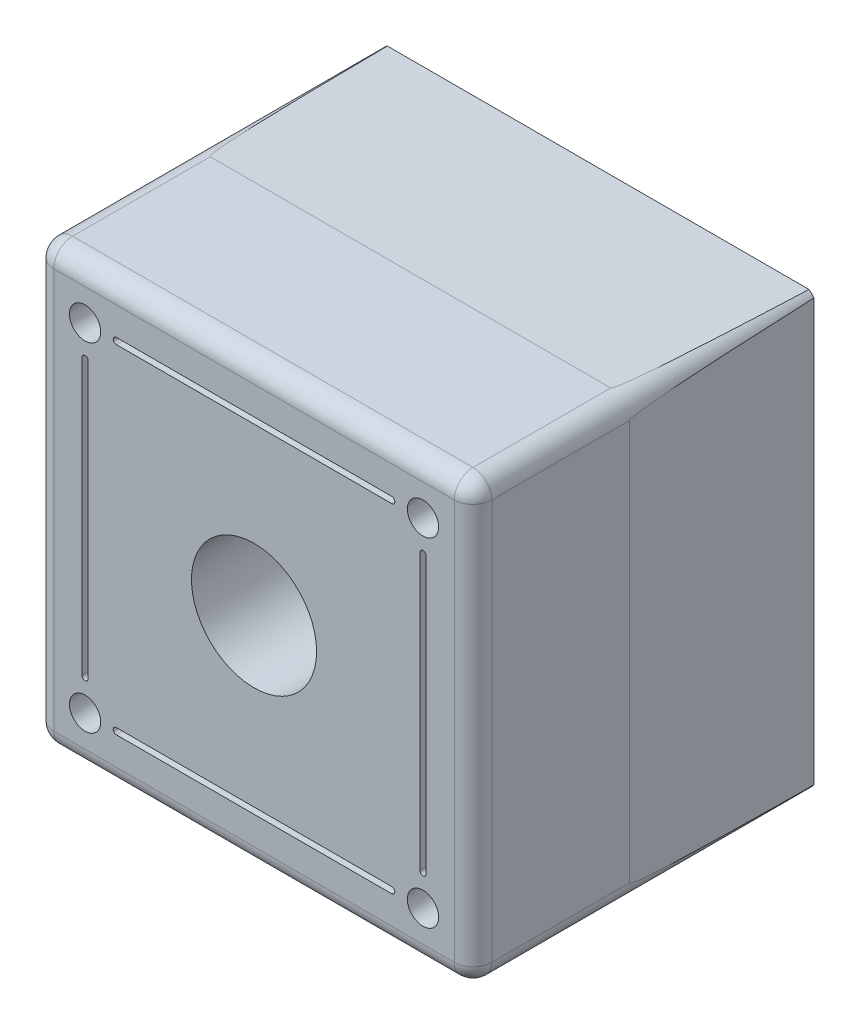
SolidWorks part; units mm, degrees
ref_plane "Front Plane" through (0, 0, 0) normal (0, 0, 1) x (1, 0, 0)
ref_plane "Top Plane" through (0, 0, 0) normal (0, 1, 0) x (1, 0, 0)
ref_plane "Right Plane" through (0, 0, 0) normal (1, 0, 0) x (0, 0, -1)
sketch "Sketch1" plane through (0, 0, 0) normal (0, 0, 1) x (1, 0, 0)
  line L1 (-35, 35) -> (35, 35)
  line L2 (-35, 35) -> (-35, -35)
  line L3 (-35, -35) -> (35, -35)
  line L4 (35, 35) -> (35, -35)
  line L5 (-35, 35) -> (35, -35) construction
  line L6 (-35, -35) -> (35, 35) construction
  point P0 (0, 0)
  dimension "D1" = 70
  dimension "D2" = 70
extrude "Boss-Extrude1" add sketch "Sketch1" against normal blind 30 draft 1
sketch "Sketch2" plane through (0, 0, 0) normal (0, 0, 1) x (1, 0, 0)
  line L4 (35, -35) -> (35, 35)
  line L5 (35, 35) -> (-35, 35)
  line L6 (-35, 35) -> (-35, -35)
  line L7 (-35, -35) -> (35, -35)
  line L8 (35, -35) -> (35, 35)
  line L9 (35, 35) -> (-35, 35)
  line L10 (-35, 35) -> (-35, -35)
  line L11 (-35, -35) -> (35, -35)
  dimension "D1" = 0
extrude "Boss-Extrude2" add sketch "Sketch2" along normal blind 25
sketch "Sketch3" plane through (0, 0, 25) normal (0, 0, 1) x (1, 0, 0)
  line L0 (35, -35) -> (35, 35) construction
  line L1 (35, 35) -> (-35, 35) construction
  circle A0 centre (27, 27) radius 2.5
  dimension "D1" = 8
  dimension "D3" = 5
  dimension "D2" = 8
extrude "Cut-Extrude1" cut sketch "Sketch3" against normal blind 25
mirror "Mirror1" about plane through (0, 0, 0) normal (1, 0, 0) of "Cut-Extrude1"
mirror "Mirror2" about plane through (0, 0, 0) normal (0, 1, 0) of "Mirror1", "Cut-Extrude1"
sketch "Sketch4" plane through (0, 0, 25) normal (0, 0, 1) x (1, 0, 0)
  line L1 (35, 35) -> (-35, 35) construction
  circle A1 centre (0, 0) radius 10
  dimension "D2" = 35
extrude "Cut-Extrude2" cut sketch "Sketch4" against normal blind 25
sketch "Sketch5" plane through (0, 0, 0) normal (0, 1, 0) x (1, 0, 0)
  line L0 (35, -25) -> (-35, -25) construction
  line L1 (0, -25) -> (0, -32) construction
  line L2 (0, -25) -> (0, -32)
  line L3 (12.6886, -25) -> (0, -25)
  arc A0 (12.6886, -25) -> (0, -32) centre (0, -17) cw
  dimension "D1" = 15
  dimension "D2" = 8
revolve "Revolve2" [suppressed] add sketch "Sketch5" angle 360 about L1
fillet "Fillet1" radius 3 8 edges at (-35, 0, 25) (35, 0, 25) (0, -35, 25) (0, 35, 25) (-35, -35, 12.5) (35, -35, 12.5) (-35, 35, 12.5) (35, 35, 12.5)
sketch "Sketch6" plane through (0, 0, 25) normal (0, 0, 1) x (1, 0, 0)
  line L0 (-22, 27) -> (22, 27) construction
  line L1 (-22, 27.5) -> (22, 27.5)
  line L2 (-22, 26.5) -> (22, 26.5)
  line L3 (-32, 35) -> (32, 35) construction
  line L4 (0, 0) -> (24.2245, 0) construction
  line L5 (-22, -27) -> (22, -27) construction
  line L6 (-22, -27.5) -> (22, -27.5)
  line L7 (-22, -26.5) -> (22, -26.5)
  line L8 (27, 22) -> (27, -22) construction
  line L9 (27.5, 22) -> (27.5, -22)
  line L10 (26.5, 22) -> (26.5, -22)
  line L11 (35, 32) -> (35, -32) construction
  line L12 (0, 0) -> (0, 18.2615) construction
  line L13 (-27, 22) -> (-27, -22) construction
  line L14 (-27.5, 22) -> (-27.5, -22)
  line L15 (-26.5, 22) -> (-26.5, -22)
  arc A0 (-22, 27.5) -> (-22, 26.5) centre (-22, 27) ccw
  arc A1 (22, 26.5) -> (22, 27.5) centre (22, 27) ccw
  circle A2 centre (27, 27) radius 2.5 construction
  circle A3 centre (-27, 27) radius 2.5 construction
  arc A4 (-22, -27.5) -> (-22, -26.5) centre (-22, -27) cw
  arc A5 (22, -26.5) -> (22, -27.5) centre (22, -27) cw
  arc A6 (27.5, 22) -> (26.5, 22) centre (27, 22) ccw
  arc A7 (26.5, -22) -> (27.5, -22) centre (27, -22) ccw
  circle A8 centre (27, -27) radius 2.5 construction
  circle A9 centre (27, 27) radius 2.5 construction
  arc A10 (-27.5, 22) -> (-26.5, 22) centre (-27, 22) cw
  arc A11 (-26.5, -22) -> (-27.5, -22) centre (-27, -22) cw
  point P2 (0, 27)
  point P18 (0, -27)
  point P25 (27, 0)
  point P39 (-27, 0)
  dimension "D3" = 5
  dimension "D4" = 5
  dimension "D6" = 5
  dimension "D8" = 5
  dimension "D1" = 1
  dimension "D2" = 8
  dimension "D5" = 1
  dimension "D7" = 8
extrude "Cut-Extrude3" cut sketch "Sketch6" against normal blind 1
